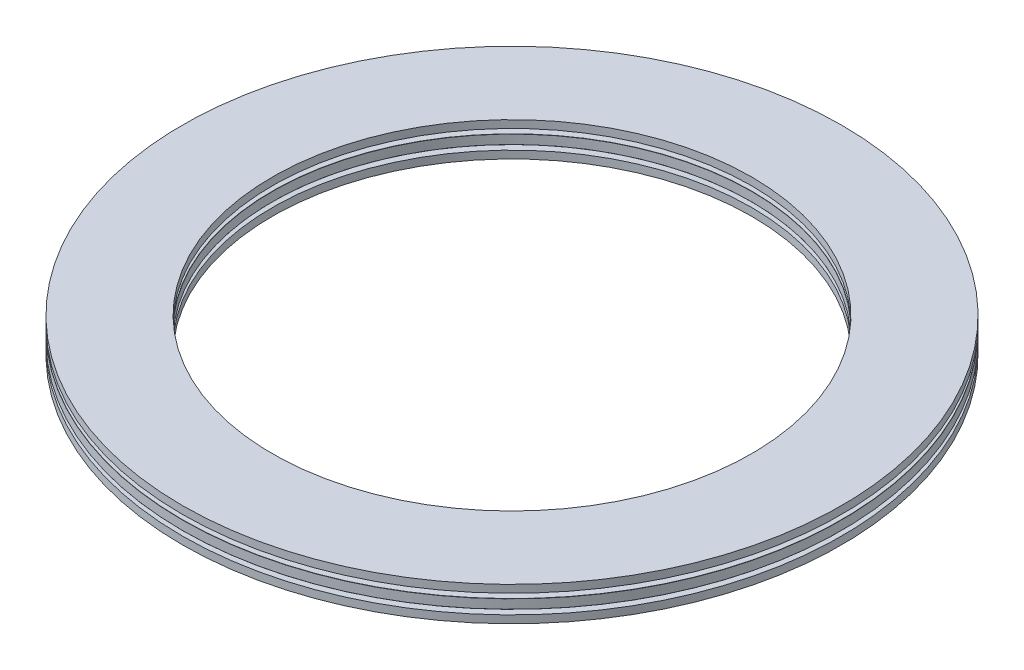
SolidWorks part; units mm, degrees
ref_plane "Front Plane" through (0, 0, 0) normal (0, 0, 1) x (1, 0, 0)
ref_plane "Top Plane" through (0, 0, 0) normal (0, 1, 0) x (1, 0, 0)
ref_plane "Right Plane" through (0, 0, 0) normal (1, 0, 0) x (0, 0, -1)
sketch "Sketch1" plane through (0, 0, 0) normal (1, 0, 0) x (0, 0, -1)
  line L0 (-34.925, 0) -> (34.925, 0) construction
  line L1 (0, -0.9922) -> (0, 0.9922) construction
  line L2 (-34.925, 0.4961) -> (-25.4, 0.4961)
  line L3 (-34.925, 0.4961) -> (-34.925, -0.4961)
  line L4 (-34.925, -0.4961) -> (-25.4, -0.4961)
  line L5 (-25.4, 0.4961) -> (-25.4, -0.4961)
  line L7 (-30.1625, 0.9922) -> (-30.1625, 0.4961) construction
  line L8 (-33.7344, 0.9922) -> (-26.5906, 0.9922) construction
  line L9 (-33.7344, 0.9922) -> (-33.7344, -0.9922) construction
  line L10 (-33.7344, -0.9922) -> (-26.5906, -0.9922) construction
  line L11 (-26.5906, 0.9922) -> (-26.5906, -0.9922) construction
  point P16 (-33.7344, 0)
  dimension "D1" = 7.1437
  dimension "OD" = 69.85
  dimension "Shaft Dia" = 50.8
  dimension "Th" = 1.9844
  dimension "D2" = 0.9922
  dimension "D3" = 9.525
revolve "Revolve1" add sketch "Sketch1" angle 360 about L1
sketch "Sketch3" plane through (0, 0, 0) normal (1, 0, 0) x (0, 0, -1)
  line L0 (-33.7344, 0.9922) -> (-33.7344, -0.9922) construction
  line L1 (-33.7344, 0) -> (-26.5906, 0)
  line L2 (-33.7344, 0) -> (-33.7344, 0.9922)
  line L3 (-33.7344, 0.9922) -> (-26.5906, 0.9922)
  line L4 (-26.5906, 0) -> (-26.5906, 0.9922)
revolve "Cut-Revolve1" cut sketch "Sketch3" angle 360 about L1
sketch "Sketch2" plane through (0, 0, 0) normal (1, 0, 0) x (0, 0, -1)
  line L1 (-33.7344, 0) -> (-26.5906, 0)
  line L2 (-33.7344, 0) -> (-33.7344, 0.9922)
  line L3 (-33.7344, 0.9922) -> (-26.5906, 0.9922)
  line L4 (-26.5906, 0) -> (-26.5906, 0.9922)
revolve "Revolve2" add sketch "Sketch2" angle 360 about L1
ref_axis "Axis1" through (0, 0.9922, 0) along (0, -1, 0)
pattern_circular "CirPattern1" count 55 over 360 about axis through (0, 0.9922, 0) along (0, -1, 0) of bodies 187 411
pattern_circular "CirPattern2" count 55 every 6.545 about axis through (0, 0.9922, 0) along (0, -1, 0) of "Cut-Revolve1"
sketch "Sketch4" plane through (0, 0, 0) normal (1, 0, 0) x (0, 0, -1)
  line L0 (-34.925, 0.4961) -> (-34.925, -0.4961) construction
  line L1 (-34.925, 0.9931) -> (-25.4, 0.9931)
  line L2 (-34.925, 0.9931) -> (-34.925, 1.8059)
  line L3 (-34.925, 1.8059) -> (-25.4, 1.8059)
  line L4 (-25.4, 0.9931) -> (-25.4, 1.8059)
  line L5 (-34.925, -1.8059) -> (-25.4, -1.8059)
  line L6 (-34.925, -1.8059) -> (-34.925, -0.9931)
  line L7 (-34.925, -0.9931) -> (-25.4, -0.9931)
  line L8 (-25.4, -1.8059) -> (-25.4, -0.9931)
  line L10 (-25.4, 0.4961) -> (-25.4, -0.4961) construction
  line L11 (0, 0) -> (-34.925, 0) construction
  line L12 (-34.925, 0) -> (34.925, 0) construction
  line L13 (0, -0.9922) -> (0, 0.9922) construction
  dimension "Ht" = 3.6119
  dimension "Washer Th" = 0.8128
  dimension "Washer ID" = 50.8
  dimension "Washer OD" = 69.85
revolve "Revolve3" add sketch "Sketch4" angle 360 about L1
fillet "Fillet1" [suppressed] radius 0.0198
fillet "Fillet2" radius 0.0198 4 edges at (0, -0.4961, -25.4) (0, 0.4961, -25.4) (0, -0.4961, -34.925) (0, 0.4961, -34.925)
fillet "Fillet3" [suppressed] radius 0.0198
equation "\"D2@Sketch1\" = \"Th@Sketch1\"*.5"
equation "\"D1@Fillet1\" = \"Th@Sketch1\"*.01"
equation "\"D1@Fillet2\" = \"D1@Fillet1\""
equation "\"D1@Fillet3\" = \"D1@Fillet1\""
equation "\"D1@Sketch1\" = 0.28125"
equation "\"Angle@CirPattern1\"= 360 / 55"
equation "\"Rollers@CirPattern1\" = 55"
equation "\"D1@CirPattern2\" = \"Rollers@CirPattern1\""
equation "\"D2@CirPattern2\" = \"Angle@CirPattern1\""
equation "\"Ht@Sketch4\"= .0781 * 2 - 0.014"
